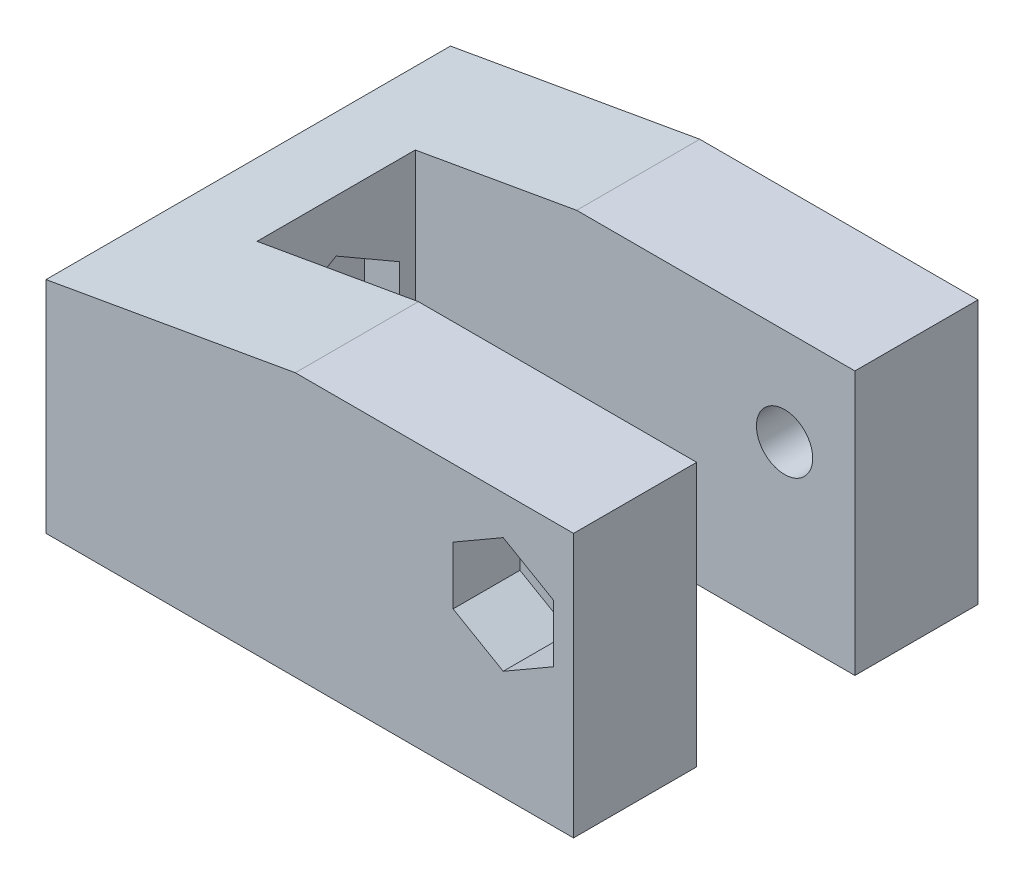
SolidWorks part; units mm, degrees
ref_plane "Front Plane" through (0, 0, 0) normal (0, 0, 1) x (1, 0, 0)
ref_plane "Top Plane" through (0, 0, 0) normal (0, 1, 0) x (1, 0, 0)
ref_plane "Right Plane" through (0, 0, 0) normal (1, 0, 0) x (0, 0, -1)
sketch "Sketch1" plane through (0, 0, 0) normal (1, 0, 0) x (0, 0, -1)
  line L1 (0, 0) -> (23, 0)
  line L2 (0, 0) -> (0, 15)
  line L3 (0, 15) -> (23, 15)
  line L4 (23, 0) -> (23, 15)
  dimension "D1" = 23
  dimension "D2" = 15
extrude "Boss-Extrude1" add sketch "Sketch1" along normal blind 30
sketch "Sketch2" plane through (30, 0, 0) normal (1, 0, 0) x (0, 0, -1)
  line L0 (11.5, 15) -> (11.5, 0) construction
  line L1 (7, 15) -> (16, 15)
  line L2 (7, 15) -> (7, 0)
  line L3 (7, 0) -> (16, 0)
  line L4 (16, 15) -> (16, 0)
  line L5 (0, 0) -> (23, 0) construction
  line L8 (23, 15) -> (0, 15) construction
  line L9 (11.5, 15) -> (11.5, 0) construction
  dimension "D1" = 9
extrude "Cut-Extrude1" cut sketch "Sketch2" against normal offset from surface (25 mm away) 5 up to face at (0, 7.5, -11.5)
sketch "Sketch3" plane through (0, 0, -23) normal (0, 0, -1) x (-1, 0, 0)
  line L1 (-30, 0) -> (-30, 15) construction
  line L2 (-30, 0) -> (0, 0) construction
  circle A0 centre (-26, 9.5) radius 1.6
  dimension "D3" = 3.2
  dimension "D1" = 9.5
  dimension "D2" = 4
extrude "Cut-Extrude2" cut sketch "Sketch3" against normal through all both and the other way through all
chamfer "Chamfer1" distance 2.5 angle 80 1 edges at (0, 15, -11.5) first distance on face at (0, 7.5, -11.5)
sketch "Sketch4" plane through (0, 0, 0) normal (-1, 0, 0) x (0, 0, 1)
  line L0 (-11.5, 12.5) -> (-11.5, 0) construction
  line L1 (0, 12.5) -> (-23, 12.5) construction
  line L2 (0, 0) -> (-23, 0) construction
  line L3 (-23, 6.25) -> (0, 6.25) construction
  line L4 (-23, 0) -> (-23, 12.5) construction
  line L5 (0, 12.5) -> (0, 0) construction
  circle A0 centre (-11.5, 6.25) radius 2.2
  dimension "D1" = 4.4
extrude "Cut-Extrude3" cut sketch "Sketch4" against normal blind 10
sketch "Sketch5" plane through (5, 0, 0) normal (1, 0, 0) x (0, 0, -1)
  line L1 (7.9, 8.3285) -> (7.9, 4.1715)
  line L2 (7.9, 4.1715) -> (11.5, 2.0931)
  line L3 (11.5, 2.0931) -> (15.1, 4.1715)
  line L4 (15.1, 4.1715) -> (15.1, 8.3285)
  line L5 (15.1, 8.3285) -> (11.5, 10.4069)
  line L6 (11.5, 10.4069) -> (7.9, 8.3285)
  circle A0 centre (11.5, 6.25) radius 3.6 construction
  dimension "D1" = 7.2
extrude "Cut-Extrude4" cut sketch "Sketch5" against normal blind 2
sketch "Sketch6" plane through (0, 0, -23) normal (0, 0, -1) x (-1, 0, 0)
  circle A0 centre (-26, 9.5) radius 3.25
  dimension "D1" = 6.5
extrude "Cut-Extrude5" cut sketch "Sketch6" against normal blind 2.5
sketch "Sketch7" plane through (0, 0, 0) normal (0, 0, 1) x (1, 0, 0)
  line L1 (23.15, 11.1454) -> (23.15, 7.8546)
  line L2 (23.15, 7.8546) -> (26, 6.2091)
  line L3 (26, 6.2091) -> (28.85, 7.8546)
  line L4 (28.85, 7.8546) -> (28.85, 11.1454)
  line L5 (28.85, 11.1454) -> (26, 12.7909)
  line L6 (26, 12.7909) -> (23.15, 11.1454)
  circle A0 centre (26, 9.5) radius 2.85 construction
  dimension "D1" = 5.7
extrude "Cut-Extrude6" cut sketch "Sketch7" against normal blind 3.8
